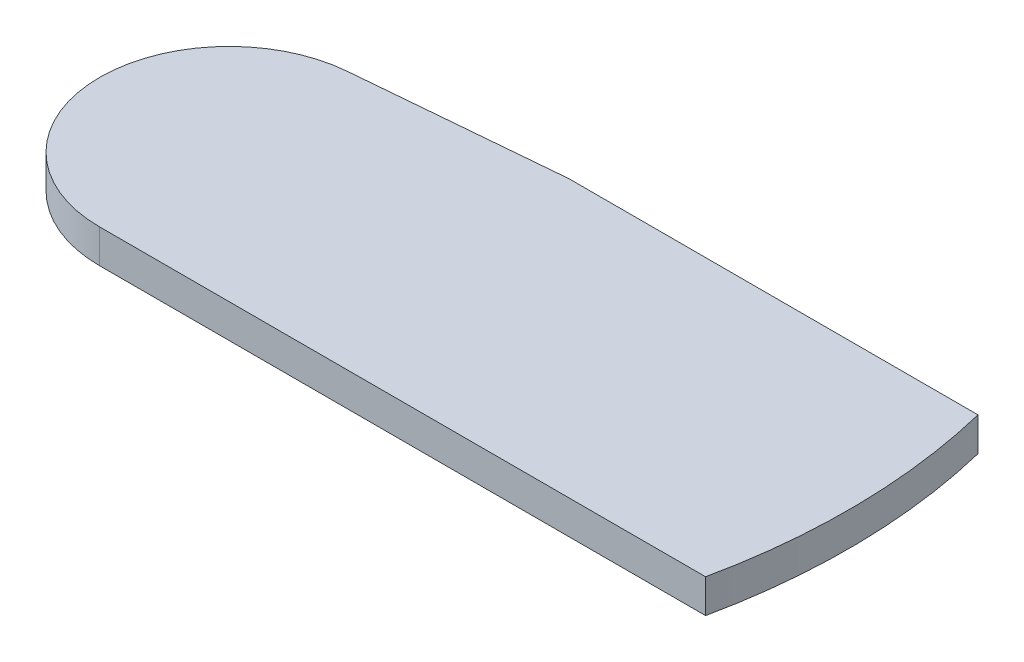
SolidWorks part; units mm, degrees
ref_plane "Płaszczyzna przednia" through (0, 0, 0) normal (0, 0, 1) x (1, 0, 0)
ref_plane "Płaszczyzna górna" through (0, 0, 0) normal (0, 1, 0) x (1, 0, 0)
ref_plane "Płaszczyzna prawa" through (0, 0, 0) normal (1, 0, 0) x (0, 0, -1)
sketch "Sketch1" plane through (0, 0, 0) normal (0, 1, 0) x (1, 0, 0)
  line L0 (-110.7065, 0) -> (22.5357, 0) construction
  line L1 (0, -110.7065) -> (0, 5424.6164) construction
  line L2 (-45.3355, 9.9619) -> (-29.5652, 11.3431)
  line L3 (-29.5652, 11.3431) -> (2.0157, 11.3431)
  line L4 (-29.5652, 11.3431) -> (-29.5652, -10)
  line L5 (-29.5652, -10) -> (2.3231, -10)
  line L7 (-44.463, -10) -> (-29.5652, -10)
  circle A0 centre (-44.463, 0) radius 10
  arc A1 (2.3231, -10) -> (2.0157, 11.3431) centre (-44.463, 0) ccw
  arc A2 (3.3507, -7.1332) -> (-12.8948, 36.6125) centre (-44.463, 0) ccw construction
  dimension "D1" = 20
  dimension "D2" = 0.5
extrude "Boss-Extrude1" add sketch "Sketch1" along normal blind 2.6 contours A0 | A0 L7 L4 L2 | L5 A1 L3 L4 region at (-33.5252, 0, -0.7119) region at (-44.463, 0, 0) region at (-13.2929, 0, -0.6549)
